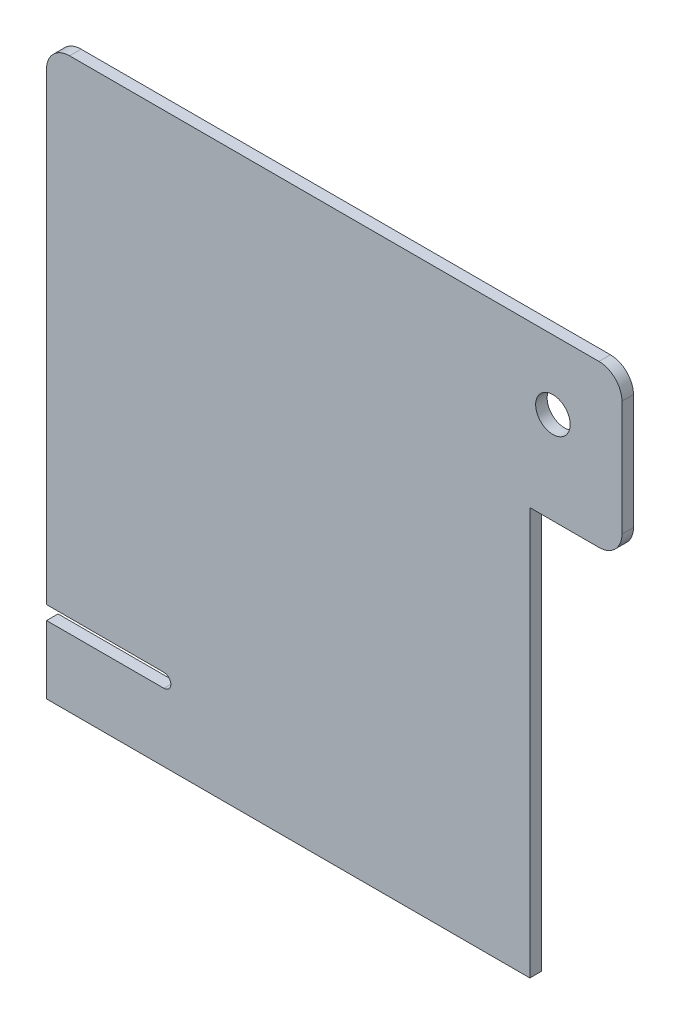
SolidWorks part; units mm, degrees
ref_plane "前视基准面" through (0, 0, 0) normal (0, 0, 1) x (1, 0, 0)
ref_plane "上视基准面" through (0, 0, 0) normal (0, 1, 0) x (1, 0, 0)
ref_plane "右视基准面" through (0, 0, 0) normal (1, 0, 0) x (0, 0, -1)
sketch "草图1" plane through (0, 0, 0) normal (0, 0, 1) x (1, 0, 0)
  line L0 (210, -237) -> (210, -247)
  line L1 (10, 0) -> (210, 0)
  line L2 (0, -10) -> (0, -237)
  line L3 (10, -247) -> (200, -247)
  line L4 (210, 0) -> (210, -237)
  line L5 (210, 0) -> (240, 0)
  line L6 (210, 0) -> (210, -70)
  line L7 (210, -70) -> (240, -70)
  line L8 (250, -10) -> (250, -60)
  line L9 (210, -247) -> (200, -247)
  line L10 (0, -237) -> (0, -247)
  line L11 (10, -247) -> (0, -247)
  arc A0 (240, 0) -> (250, -10) centre (240, -10) cw
  arc A1 (240, -70) -> (250, -60) centre (240, -60) ccw
  arc A4 (10, 0) -> (0, -10) centre (10, -10) ccw
  point P10 (250, 0)
  point P13 (250, -70)
  point P18 (0, -247)
  point P21 (0, 0)
  dimension "D5" = 10
  dimension "D1" = 247
  dimension "D2" = 210
  dimension "D3" = 40
  dimension "D4" = 70
extrude "凸台-拉伸1" add sketch "草图1" along normal blind 5 contours L3 L9 L0 L4 L1 A4 L2 L10 L11 | L6 L7 A1 L8 A0 L5
sketch "草图2" plane through (0, 0, 5) normal (0, 0, 1) x (1, 0, 0)
  line L0 (160.7676, 0) -> (160.7676, -30) construction
  line L1 (10, 0) -> (240, 0) construction
  line L2 (250, -30) -> (0, -30) construction
  line L3 (250, -10) -> (250, -60) construction
  line L4 (0, -10) -> (0, -247) construction
  line L5 (210, -70) -> (210, 0) construction
  line L6 (210, -30) -> (220, -30) construction
  circle A0 centre (220, -30) radius 7.5
  dimension "D3" = 15
  dimension "D1" = 30
  dimension "D2" = 10
extrude "切除-拉伸1" cut sketch "草图2" against normal blind 5
sketch "草图3" plane through (0, 0, 0) normal (-1, 0, 0) x (0, 0, 1)
  line L1 (0, -10) -> (0, -247) construction
  line L3 (5, -10) -> (5, -247) construction
  line L5 (5, -214.5) -> (6.3865, -214.5) construction
  line L16 (0, -217.5) -> (5, -217.5)
  line L19 (0, -217.5) -> (0, -211.5)
  line L20 (0, -211.5) -> (5, -211.5)
  line L21 (5, -217.5) -> (5, -211.5)
  point P15 (0, -214.5)
extrude "切除-拉伸3" cut sketch "草图3" against normal blind 51
sketch "草图4" plane through (0, 0, 5) normal (0, 0, 1) x (1, 0, 0)
  line L0 (51, -211.5) -> (51, -217.5) construction
  line L1 (51, -211.5) -> (51, -217.5)
  arc A0 (51, -217.5) -> (51, -211.5) centre (51, -214.5) ccw
extrude "切除-拉伸4" cut sketch "草图4" against normal up to next
